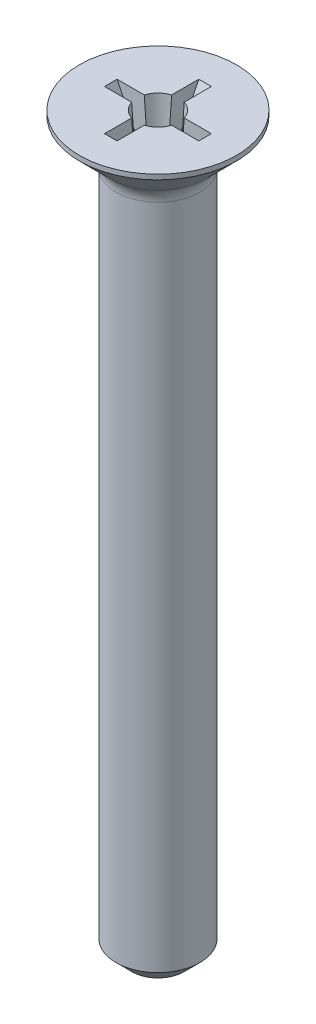
SolidWorks part; units mm, degrees
material "AISI 304"
ref_plane "Спереди" through (0, 0, 0) normal (0, 0, 1) x (1, 0, 0)
ref_plane "Сверху" through (0, 0, 0) normal (0, 1, 0) x (1, 0, 0)
ref_plane "Справа" through (0, 0, 0) normal (1, 0, 0) x (0, 0, -1)
sketch "Эскиз1" plane through (0, 0, 0) normal (0, 0, 1) x (1, 0, 0)
  line L0 (0, 0) -> (-0.5, 0)
  line L1 (-0.5, 0) -> (-0.8, 0.3)
  line L2 (-0.8, 0.3) -> (-0.8, 13.04)
  line L3 (-0.9172, 13.3228) -> (-1.5, 13.9057)
  line L4 (-1.5, 13.9057) -> (-1.5, 14)
  line L5 (-0.4, 14) -> (0, 14) construction
  line L9 (-0.3203, 12.86) -> (0, 12.86)
  line L13 (0, 12.86) -> (0, 0)
  line L14 (-1.2, 13.04) -> (-0.8, 13.04) construction
  line L17 (-0.3203, 12.86) -> (-0.4, 14)
  line L19 (-0.4, 14) -> (-1.5, 14)
  line L24 (-0.8, 13.04) -> (-0.8, 13.2057) construction
  line L25 (-0.8, 13.2057) -> (-0.9172, 13.3228) construction
  line L26 (-0.5, 0) -> (-0.8, 0) construction
  line L27 (-0.8, 0) -> (-0.8, 0.3) construction
  arc A0 (-0.8, 13.04) -> (-0.9172, 13.3228) centre (-1.2, 13.04) ccw
  point P14 (0.8, 0.3)
  point P15 (1.5, 14)
  dimension "r" = 0.4
  dimension "D1" = 45
  dimension "D2" = 4
  dimension "k" = 0.96
  dimension "d" = 1.6
  dimension "z" = 0.3
  dimension "L" = 14
  dimension "m" = 1.14
  dimension "Dk" = 3
revolve "Повернуть1" add sketch "Эскиз1" angle 360 about L13
cosmetic thread "резьба" parameters "D1"=14, "D2"=1.2
sketch "Эскиз3" plane through (0, 0, 0) normal (0, 0, 1) x (1, 0, 0)
  line L0 (-0.9, 14) -> (-0.344, 12.86)
  line L1 (0, 0) -> (0, -0.5634) construction
  line L2 (0.9, 14) -> (0.344, 12.86)
  line L3 (-0.9, 14) -> (0.9, 14)
  line L4 (0.4, 14) -> (-0.4, 14) construction
  line L5 (-0.344, 12.86) -> (0.344, 12.86)
  line L6 (0.3203, 12.86) -> (-0.3203, 12.86) construction
  dimension "D1" = 1.8
  dimension "D2" = 52
extrude "Вырез-Вытянуть2" cut sketch "Эскиз3" against normal blind 0.12 and the other way blind 0.12
sketch "Эскиз4" plane through (0, 0, 0) normal (1, 0, 0) x (0, 0, -1)
  line L0 (0, 0) -> (0, -0.25) construction
  line L1 (-0.5, 0) -> (0.5, 0) construction
  line L2 (-0.344, 12.86) -> (-0.9, 14)
  line L3 (1.5, 14) -> (-1.5, 14) construction
  line L4 (0.344, 12.86) -> (0.9, 14)
  line L5 (-0.344, 12.86) -> (0.344, 12.86)
  line L6 (-0.9, 14) -> (0.9, 14)
  line L7 (-0.12, 12.86) -> (0.12, 12.86) construction
  dimension "D1" = 1.8
  dimension "D2" = 52
extrude "Вырез-Вытянуть3" cut sketch "Эскиз4" against normal blind 0.12 and the other way blind 0.12
equation "\"Thread_length@ThreadCosmetic\" =  (  ( sgn (  ( \"Length@BodySke\" - \"Advance@BodySke\" *  3.0  - \"Head_ht@BodySke\" )  - \"Thread_nom@BodySke\" )  - 1 )  *  (  ( \"Length@BodySke\" - \"Advance@BodySke\" *  3.0  - \"Head_ht@BodySke\" )  - \"Thread_nom@BodySke\" )  )  /  - 2 + \"Thread_nom@BodySke\""
equation "\"Num_threads\"=  int ( \"Thread_length@ThreadCosmetic\" / \"Advance@BodySke\" +  0.999  )  +  1"
